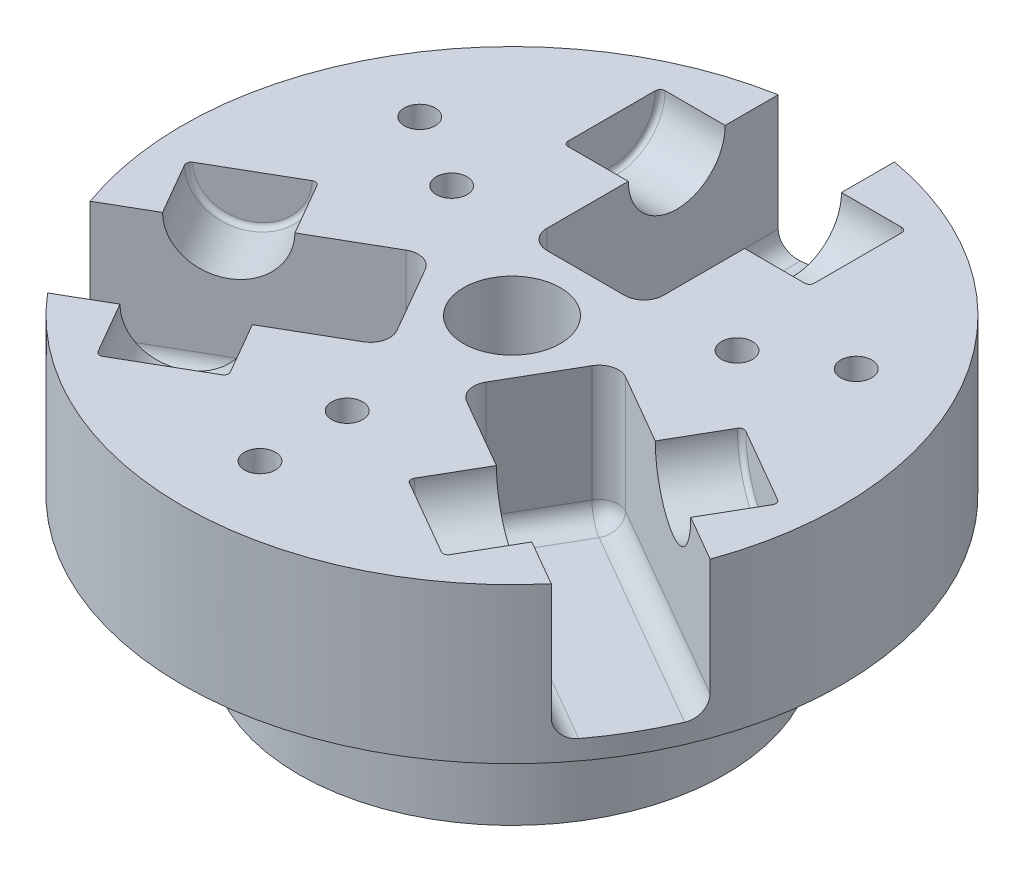
SolidWorks part; units mm, degrees
material "7075-T6 (SN)"
ref_plane "Front" through (0, 0, 0) normal (0, 0, 1) x (1, 0, 0)
ref_plane "Top" through (0, 0, 0) normal (0, 1, 0) x (1, 0, 0)
ref_plane "Right" through (0, 0, 0) normal (1, 0, 0) x (0, 0, -1)
sketch "Sketch1" plane through (0, 0, 0) normal (0, 1, 0) x (1, 0, 0)
  line L0 (0, 0) -> (0, 16) construction
  line L1 (0, 0) -> (-13.8564, -8) construction
  line L2 (0, 0) -> (13.8564, -8) construction
  line L3 (-12.7, 7.3323) -> (-12.7, 16) construction
  line L4 (-12.7, 16) -> (12.7, 16) construction
  line L5 (12.7, 16) -> (12.7, 7.3323) construction
  line L6 (-20.2064, 2.9985) -> (-12.7, 7.3323) construction
  line L7 (-20.2064, 2.9985) -> (-7.5064, -18.9985) construction
  line L8 (-7.5064, -18.9985) -> (0, -14.6647) construction
  line L9 (0, -14.6647) -> (7.5064, -18.9985) construction
  line L10 (7.5064, -18.9985) -> (20.2064, 2.9985) construction
  line L11 (20.2064, 2.9985) -> (12.7, 7.3323) construction
  line L12 (-20.2064, 2.9985) -> (-12.7, 16) construction
  line L13 (12.7, 16) -> (20.2064, 2.9985) construction
  line L14 (7.5064, -18.9985) -> (-7.5064, -18.9985) construction
  circle A0 centre (0, 0) radius 12.7 construction
  circle A1 centre (0, 0) radius 17
  dimension "D4" = 25.4
  dimension "D5" = 34
  dimension "D1" = 120
  dimension "D2" = 120
  dimension "D3" = 16
extrude "Boss-Extrude1" add sketch "Sketch1" along normal blind 14
ref_axis "Axis1" through (0, 40.005, 0) along (0, -1, 0)
sketch "Sketch9" plane through (0, 14, 0) normal (0, 1, 0) x (1, 0, 0)
  line L0 (0, 0) -> (0, 3.81) construction
  line L2 (-3, 17) -> (3, 17)
  line L3 (3, 17) -> (3, 3.81)
  line L4 (3, 3.81) -> (-3, 3.81)
  line L5 (-3, 3.81) -> (-3, 17)
  circle A1 centre (0, 0) radius 17 construction
  dimension "D1" = 6
  dimension "D3" = 3.81
extrude "Cut-Extrude1" cut sketch "Sketch9" against normal through all contours L5 L2 L3 L4
sketch "Sketch10" plane through (0, 0, 0) normal (1, 0, 0) x (0, 0, -1)
  line L2 (16.7332, 14) -> (-17, 14) construction
  line L3 (-17, 0) -> (16.7332, 0) construction
  line L5 (11.5, 14) -> (11.5, 0) construction
  circle A0 centre (11.5, 7) radius 2.5
  dimension "D1" = 5
  dimension "D2" = 11.5
extrude "Cut-Extrude2" cut sketch "Sketch10" against normal mid plane 12.7
fillet "Fillet2" radius 1 2 edges at (3, 7, -3.81) (-3, 7, -3.81)
pattern_circular "CirPattern2" count 3 over 360 about axis through (0, 40.005, 0) along (0, -1, 0) of "Cut-Extrude1", "Cut-Extrude2", "Fillet2"
ref_plane "Plane1" through (0, 7, 0) normal (0, 1, 0) x (1, 0, 0)
sketch "Sketch12" plane through (0, 7, 0) normal (0, 1, 0) x (1, 0, 0)
  circle A0 centre (0, 0) radius 20
  dimension "D1" = 40
extrude "Cut-Extrude3" cut sketch "Sketch12" along normal blind 10 contours A0
sketch "Sketch13" plane through (0, 0, 0) normal (0, -1, 0) x (1, 0, 0)
  circle A0 centre (0, 0) radius 17
  arc A1 (12.9914, 10.9647) -> (-12.9914, 10.9647) centre (0, 0) ccw construction
extrude "Boss-Extrude2" add sketch "Sketch13" along normal blind 1
sketch "Sketch14" plane through (0, -1, 0) normal (0, -1, 0) x (1, 0, 0)
  circle A0 centre (0, 0) radius 9.652
  circle A1 centre (0, 0) radius 11
  dimension "D1" = 19.304
  dimension "D2" = 22
sketch "Sketch15" plane through (0, 7, 0) normal (0, 1, 0) x (1, 0, 0)
  line L0 (0, 0) -> (8.6603, 5) construction
  line L2 (0, -10) -> (0, 0) construction
  line L3 (0, 0) -> (-8.6603, 5) construction
  circle A0 centre (0, 0) radius 10 construction
  dimension "D1" = 20
  dimension "D2" = 120
  dimension "D3" = 120
hole_wizard "M2x0.4 Tapped Hole3" positions "Sketch19" profile "Sketch18" tap size "M2x0.4" standard "ANSI Metric"
sketch "Sketch19" plane through (0, 7, 0) normal (0, 1, 0) x (1, 0, 0)
  line L0 (-11.2583, 6.5) -> (0, 0) construction
  line L1 (0, 0) -> (11.2583, 6.5) construction
  line L2 (0, -13) -> (0, 0) construction
  circle A0 centre (0, 0) radius 8.5
  circle A1 centre (0, 0) radius 13
  point P12 (-11.2583, 6.5)
  point P13 (11.2583, 6.5)
  point P14 (0, -13)
  point P21 (-7.3612, 4.25)
  point P22 (7.3612, 4.25)
  point P23 (0, -8.5)
  dimension "D1" = 17
  dimension "D4" = 26
  dimension "D2" = 120
  dimension "D3" = 120
sketch "Sketch18" plane through (-11.2583, 7, -6.5) normal (1, 0, 0) x (0, 0, 1)
  line L0 (0, 0) -> (0, 7.4807)
  line L1 (0, 7.4807) -> (0.8, 7)
  line L2 (0.8, 7) -> (0.8, 0)
  line L5 (0.8, 0) -> (0, 0)
  line L10 (0, 7.4807) -> (-0.8, 7) construction
  line L11 (0, -6.35) -> (0, 107.95) construction
  dimension "Tap Drill Dia." = 1.6
  dimension "Tap Drill Depth" = 7
  dimension "Drill Angle" = 118
cosmetic thread "Hole Thread9" parameters "D1"=7, "D2"=2
cosmetic thread "Hole Thread10" parameters "D1"=7, "D2"=2
cosmetic thread "Hole Thread11" parameters "D1"=7, "D2"=2
cosmetic thread "Hole Thread12" parameters "D1"=7, "D2"=2
cosmetic thread "Hole Thread13" parameters "D1"=7, "D2"=2
cosmetic thread "Hole Thread14" parameters "D1"=7, "D2"=2
fillet "Fillet3" radius 1 15 edges at (-4.9068, 0, -0.293) (-3.2996, 0, 1.905) (-2.1997, 0, 4.3959) (2.1997, 0, 4.3959) (4.9068, 0, -0.293) (-2.7071, 0, -4.1029) (0, 0, -3.81) (2.7071, 0, -4.1029) (3.2996, 0, 1.905)
extrude "Boss-Extrude3" add sketch "Sketch14" along normal blind 7
sketch "Sketch20" plane through (0, -1, 0) normal (0, -1, 0) x (1, 0, 0)
  circle A0 centre (0, 0) radius 2.5
  dimension "D1" = 5
extrude "Cut-Extrude5" cut sketch "Sketch20" against normal up to surface (8 mm away) up to face at (-11.2583, 7, -5.7)
fillet "Fillet4" radius 0.25 6 edges at (13.1343, 4.5, 0.2507) (6.7843, 4.5, 11.2493) (6.35, 4.5, -11.5) (-6.35, 4.5, -11.5) (-6.7843, 4.5, 11.2493) (-13.1343, 4.5, 0.2507)
